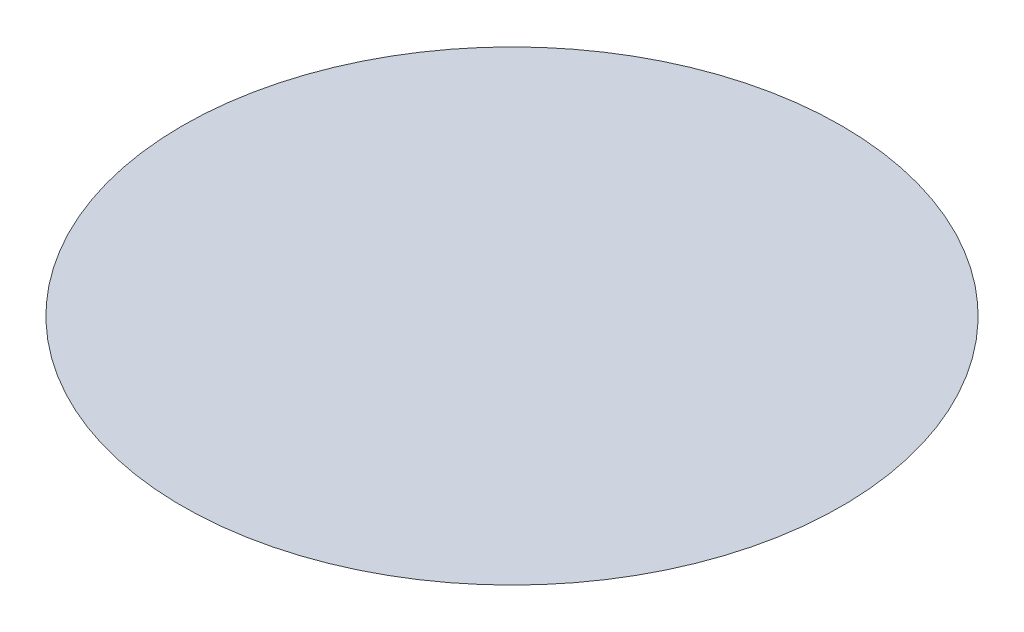
SolidWorks part; units mm, degrees
material "Alloy Steel"
ref_plane "Front Plane" through (0, 0, 0) normal (0, 0, 1) x (1, 0, 0)
ref_plane "Top Plane" through (0, 0, 0) normal (0, 1, 0) x (1, 0, 0)
ref_plane "Right Plane" through (0, 0, 0) normal (1, 0, 0) x (0, 0, -1)
sketch "Sketch1" plane through (0, 0, 0) normal (0, 0, 1) x (1, 0, 0)
  line L0 (0, 0) -> (0, 24.5)
  line L1 (0, 24.5) -> (95.9217, 24.5)
  arc A0 (0, 0) -> (95.9217, 24.5) centre (0, 200.025) ccw
  dimension "D1" = 200.025
  dimension "D2" = 24.5
revolve "Revolve1" add sketch "Sketch1" angle 360 about L0
